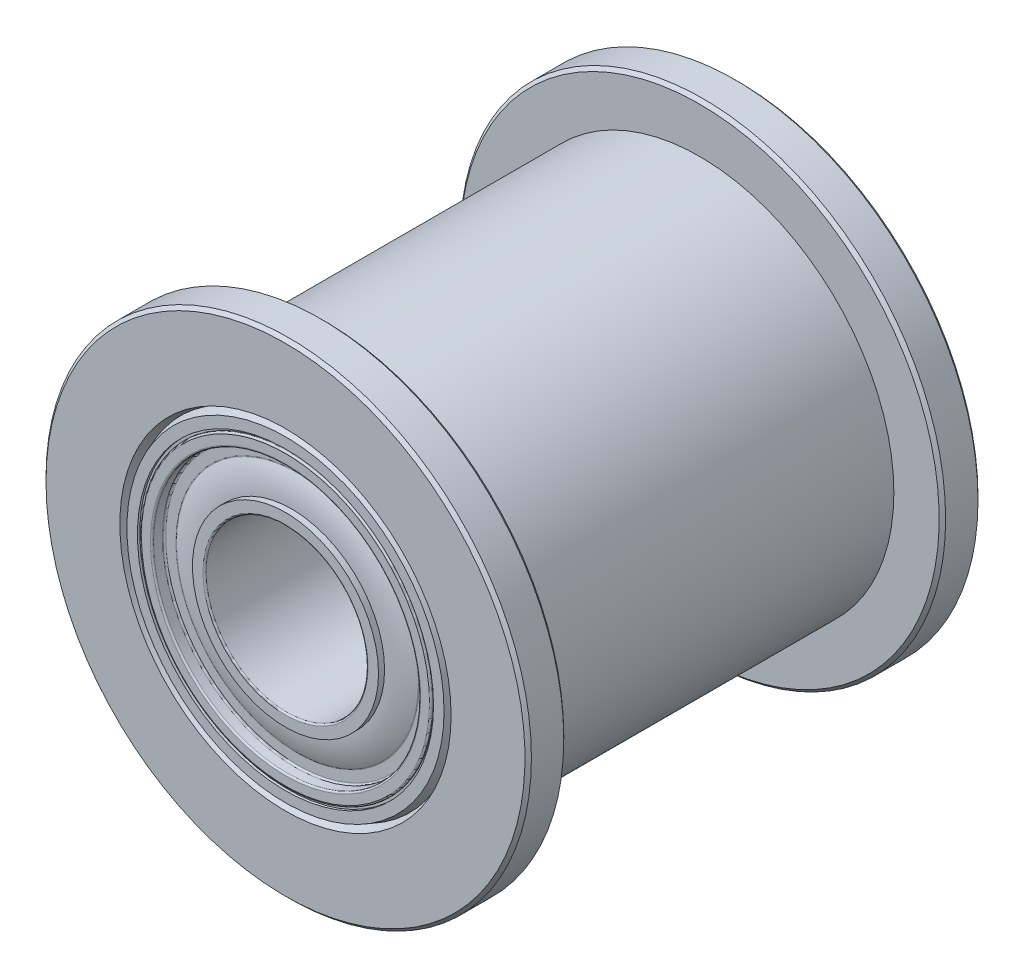
SolidWorks part; units mm, degrees
note: '?' marks a value the reader was unsure of.
ref_plane "Front" through (0, 0, 0) normal (0, 0, 1) x (1, 0, 0)
ref_plane "Top" through (0, 0, 0) normal (0, 1, 0) x (1, 0, 0)
ref_plane "Right" through (0, 0, 0) normal (1, 0, 0) x (0, 0, -1)
sketch "Sketch1" plane through (0, 0, 0) normal (1, 0, 0) x (0, 0, -1)
  line L0 (-7, 0) -> (7, 0) construction
  line L1 (7, 7.5) -> (7, -7.5) construction
  line L2 (7, 7.5) -> (5.8, 7.5) construction
  line L3 (7, 2.5) -> (7, -2.5) construction
  line L4 (7, 6) -> (7, -6) construction
  line L5 (4.5, 0) -> (-4.5, 0) construction
  line L6 (5.8, 7.5) -> (5.8, 6) construction
  dimension "D3" = 1.2
  dimension "Width" = 14
  dimension "OD" = 15
  dimension "ID" = 5
  dimension "Diameter" = 12
  dimension "Max Belt Width" = 9
  dimension "Groove Depth" = 1.5
sketch "Sketch2" plane through (0, 0, 0) normal (1, 0, 0) x (0, 0, -1)
  line L0 (7, 2.5) -> (0, 2.5)
  line L1 (7, 2.5) -> (7, 2.875)
  line L2 (7, 7.5) -> (7, -7.5) construction
  line L3 (7, 2.875) -> (6.625, 2.875) construction
  line L4 (6.8125, 4.125) -> (6.8125, 2.875) construction
  line L5 (7, 4.5) -> (0, 4.5)
  line L6 (6.625, 3.75) -> (6.625, 4.125)
  line L7 (7, 4.5) -> (7, 4.125)
  line L8 (7, 4.125) -> (6.625, 4.125)
  line L9 (6.625, 4.125) -> (6.625, 2.875) construction
  line L10 (0, 4.5) -> (0, 2.5)
  line L11 (6.8125, 2.875) -> (7, 2.875)
  arc A0 (6.625, 3.75) -> (6.8125, 2.875) centre (4.6771, 2.875) cw
  dimension "D1" = 1.5
  dimension "D2" = 0.375
revolve "Revolve1" add sketch "Sketch2" angle 360 about L0
mirror "Mirror1" about plane through (0, 0, 0) normal (0, 0, 1) of bodies 108
sketch "Sketch3" plane through (0, 0, 0) normal (1, 0, 0) x (0, 0, -1)
  line L0 (5.8, 7.5) -> (7, 7.5)
  line L1 (7, 7.5) -> (7, 5.1184)
  line L2 (7, 7.5) -> (7, -7.5) construction
  line L3 (7, 5.1184) -> (6.7, 5.0092)
  line L4 (6.7, 5.0092) -> (7, 4.9)
  line L5 (7, 4.9) -> (7, 4.575)
  line L6 (6.925, 4.5) -> (6.925, 4.575)
  line L7 (7, 4.5) -> (-7, 4.5) construction
  line L8 (6.925, 4.575) -> (7, 4.575)
  line L9 (5.8, 7.5) -> (5.8, 6)
  line L10 (5.8, 6) -> (-5.8, 6)
  line L11 (0, 6) -> (0, 4.5) construction
  line L12 (-6.925, 4.5) -> (6.925, 4.5)
  line L13 (-5.8, 7.5) -> (-5.8, 6)
  line L14 (-6.925, 4.575) -> (-7, 4.575)
  line L15 (-6.925, 4.5) -> (-6.925, 4.575)
  line L16 (-7, 4.9) -> (-7, 4.575)
  line L17 (-6.7, 5.0092) -> (-7, 4.9)
  line L18 (-7, 5.1184) -> (-6.7, 5.0092)
  line L19 (-7, 7.5) -> (-7, 5.1184)
  line L20 (-5.8, 7.5) -> (-7, 7.5)
  line L21 (6.7, 5.0092) -> (7, 5.0092) construction
  line L22 (6.85, 5.0092) -> (6.85, 4.5) construction
  dimension "D1" = 40
  dimension "D2" = 0.3
  dimension "D3" = 0.075
  dimension "D4" = 0.4
revolve "Revolve2" add sketch "Sketch3" angle 360 about L0
sketch "Sketch4" plane through (0, 0, 0) normal (0, 0, 1) x (1, 0, 0)
  line L0 (-0.6, 6) -> (0.6, 6)
  line L1 (-0.6, 6) -> (-0.6, 5.4) construction
  line L2 (-0.6, 5.4) -> (0.6, 5.4) construction
  line L3 (0.6, 5.4) -> (0.6, 6) construction
  line L4 (0, 6) -> (0, 5.4) construction
  arc A0 (0.6, 6) -> (-0.6, 6) centre (0, 6) cw
  dimension "D1" = 0.6
  dimension "D3" = 1.2
extrude "Cut-Extrude1" [suppressed] cut sketch "Sketch4" against normal up to surface and the other way up to surface
fillet "Fillet1" [suppressed] radius 0.05
pattern_circular "CirPattern3" [suppressed] count 20 over 360
chamfer "Chamfer1" distance 0.1 angle 45 4 edges at (7.5, 0, -7) (7.5, 0, -5.8) (7.5, 0, 5.8) (7.5, 0, 7)
fillet "Fillet2" radius 0.05 10 edges at (2.5, 0, -7) (2.5, 0, 7) (4.5, 0, 7) (4.125, 0, 7) (4.125, 0, 6.625) (3.75, 0, 6.625) (2.875, 0, -7) (3.75, 0, -6.625) (4.125, 0, -7) (4.5, 0, -7)
combine bodies "Combine1" operation type add bodies to combine 110 109
ref_axis "Center Axis 1" through (0, 0, -6.95) along (0, 0, 1)?
ref_plane "Contact Plane 1" through (0, 0, -4.5) normal (0, 0, 1) x (1, 0, 0)
ref_plane "Contact Plane 2" through (0, 0, 4.5) normal (0, 0, 1) x (1, 0, 0)
equation "\"D1@Sketch4\"=\"Groove Depth@Sketch1\"/2.5"
equation "\"D3@Sketch4\"=\"Diameter@Sketch1\"/10"
equation "\"D2@Sketch3\"=\"D3@Sketch1\"/4"
equation "\"D1@Sketch2\"=(\"OD@Sketch1\"-\"Diameter@Sketch1\")/2"
equation "\"D2@Sketch2\"=\"D1@Sketch2\"/4"
equation "\"D3@Sketch3\"=\"D2@Sketch3\"/4"
equation "\"D4@Sketch3\"=\"D3@Sketch1\"/3"
